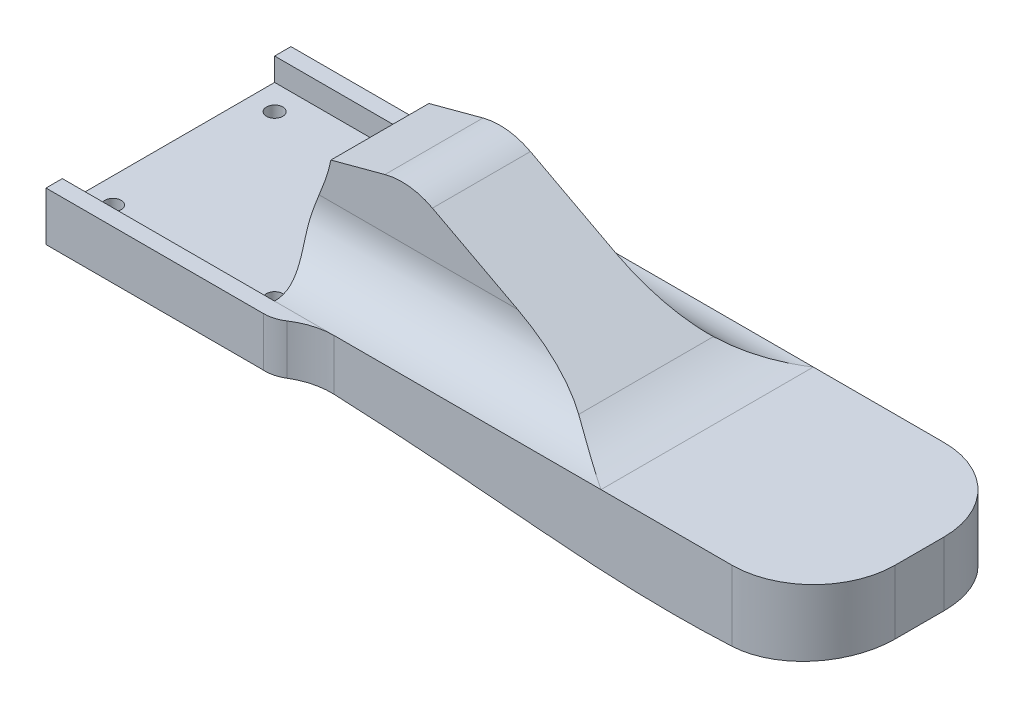
SolidWorks part; units mm, degrees
note: The reader was unsure of these and kept them because the rebuilt part matched: shared geometry of "Sketch1<4>", "Sketch1<5>".
ref_plane "Front Plane" through (0, 0, 0) normal (0, 0, 1) x (1, 0, 0)
ref_plane "Top Plane" through (0, 0, 0) normal (0, 1, 0) x (1, 0, 0)
ref_plane "Right Plane" through (0, 0, 0) normal (1, 0, 0) x (0, 0, -1)
sketch "Sketch1" plane through (0, 0, 0) normal (0, 1, 0) x (1, 0, 0)
  line L0 (-32.5, -37.5) -> (-32.5, 37.5)
  line L1 (-32.5, 32.5) -> (32.5, 32.5)
  line L2 (-32.5, 32.5) -> (-32.5, -32.5)
  line L3 (-32.5, -32.5) -> (32.5, -32.5)
  line L4 (32.5, 32.5) -> (32.5, -32.5)
  line L5 (-32.5, 32.5) -> (32.5, -32.5) construction
  line L6 (-32.5, -32.5) -> (32.5, 32.5) construction
  line L7 (-32.5, 37.5) -> (197.5, 37.5)
  line L9 (-32.5, -37.5) -> (197.5, -37.5)
  line L10 (197.5, 37.5) -> (197.5, -37.5)
  circle A0 centre (-24.7487, 24.7487) radius 2.5
  circle A1 centre (24.7487, 24.7487) radius 2.5
  circle A2 centre (24.7487, -24.7487) radius 2.5
  circle A3 centre (-24.7487, -24.7487) radius 2.5
  point P0 (0, 0)
  point P17 (0, 0)
  dimension "D3" = 5
  dimension "D1" = 65
  dimension "D2" = 65
  dimension "D4" = 35
  dimension "D6" = 5
  dimension "D7" = 5
  dimension "D8" = 230
  dimension "D5" = 4
extrude "Boss-Extrude1" add sketch "Sketch1" against normal blind 15 contours L7 L10 L9 L0
extrude "Cut-Extrude2" cut sketch "Sketch1<4>" against normal blind 7 contours L4 L3 L2 L1
sketch "Sketch1<4>" plane through (0, 0, 0) normal (0, 1, 0) x (1, 0, 0) same geometry as "Sketch1"
extrude "Cut-Extrude3" cut sketch "Sketch1<5>" against normal through all contours A1 | A0 | A3 | A2
sketch "Sketch1<5>" plane through (0, 0, 0) normal (0, 1, 0) x (1, 0, 0) same geometry as "Sketch1"
sketch "Sketch2" plane through (0, -15, 0) normal (0, -1, 0) x (1, 0, 0)
  circle A0 centre (24.7487, -24.7487) radius 5
  circle A1 centre (24.7487, 24.7487) radius 5
  circle A2 centre (-24.7487, 24.7487) radius 5
  circle A3 centre (-24.7487, -24.7487) radius 5
  dimension "D1" = 10
  dimension "D2" = 10
  dimension "D3" = 10
  dimension "D4" = 10
extrude "Cut-Extrude4" cut sketch "Sketch2" against normal blind 3.5
sketch "Sketch3" plane through (0, 0, 0) normal (0, 0, 1) x (1, 0, 0)
  line L0 (-32.5, -15) -> (197.5, -15) construction
  line L1 (-32.5, -15) -> (197.5, -15)
  line L2 (197.5, -15) -> (197.5, -19.5838)
  line L3 (197.5, -15) -> (32.5, -15)
  spline S0 degree 3 poles (32.5, -15) (112.4206, -16.95) (132.0862, -26.2638) (197.5, -19.5838) knots 0 0 0 0 1 1 1 1
  point P2 (32.5, -15)
  dimension "D1" = 32.5
extrude "Boss-Extrude2" add sketch "Sketch3" along normal up to surface and the other way up to surface contours L1 S0 L2 up to face at (82.5, -7.5, 37.5) other way up to face at (82.5, -7.5, -37.5)
sketch "Sketch5" plane through (0, 0, 0) normal (0, 0, 1) x (1, 0, 0)
  line L0 (32.5, 0) -> (122.5, 0)
  line L1 (-32.5, 0) -> (197.5, 0) construction
  line L2 (122.5, 0) -> (56.3728, 35)
  line L4 (56.3728, 35) -> (32.2247, 28.5295)
  line L5 (56.3728, 35) -> (6.6303, 35) construction
  spline S0 degree 3 poles (1828.3596, -880.1128) (-1762.7134, 869.2198) (1754.9253, -932.7195) (-1572.3821, 1220.0971) knots -2.573462 -2.573462 -2.573462 -2.573462 3.59769 3.59769 3.59769 3.59769 only from (32.5, 0) to (32.6336, 31.4306) construction
  spline S1 degree 3 poles (32.5, 0) (21.7449, 11.242) (29.9288, 16.3001) (32.2247, 28.5295) knots 0 0 0 0 0.747787 0.747787 0.747787 0.747787
  dimension "D1" = 90
  dimension "D2" = 25
  dimension "D3" = 15
  dimension "D4" = 35
extrude "Boss-Extrude3" add sketch "Sketch5" along normal blind 15 and the other way blind 15 contours L2 L4 S1 L0
fillet "Fillet6" radius 20 1 edges at (56.3728, 35, 0)
fillet "Fillet7" radius 40 1 edges at (122.5, 0, 0)
sketch "Sketch7" plane through (0, 0, 0) normal (0, 1, 0) x (1, 0, 0)
  line L0 (37.5, 68.5506) -> (37.5, -57.618) construction
  line L1 (32.5, 32.5) -> (32.5, -32.5) construction
  line L2 (37.5, 32.5) -> (208.6801, 32.5)
  line L3 (208.6801, 32.5) -> (208.6801, 56.4361)
  line L4 (208.6801, 56.4361) -> (37.5, 56.4361)
  line L5 (37.5, 56.4361) -> (37.5, 32.5)
  line L6 (0, 0) -> (19.575, 0) construction
  line L7 (208.6801, -56.4361) -> (37.5, -56.4361)
  line L8 (208.6801, -32.5) -> (208.6801, -56.4361)
  line L9 (37.5, -32.5) -> (208.6801, -32.5)
  line L10 (37.5, -56.4361) -> (37.5, -32.5)
  line L11 (-32.5, 37.5) -> (197.5, 37.5) construction
  dimension "D1" = 5
  dimension "D2" = 5
extrude "Cut-Extrude7" cut sketch "Sketch7" against normal through all both and the other way through all
fillet "Fillet10" radius 20 2 edges at (37.5, -7.5668, 32.5) (37.5, -7.5668, -32.5)
fillet "Fillet11" radius 10 1 edges at (37.5, -7.5668, -37.5)
fillet "Fillet12" radius 10 1 edges at (37.5, -7.5668, 37.5)
fillet "Fillet14" radius 17.5 1 edges at (82.4665, 0, -15)
fillet "Fillet15" radius 17.5 1 edges at (82.4665, 0, 15)
fillet "Fillet16" radius 25 2 edges at (197.5, -9.7919, 32.5) (197.5, -9.7919, -32.5)
